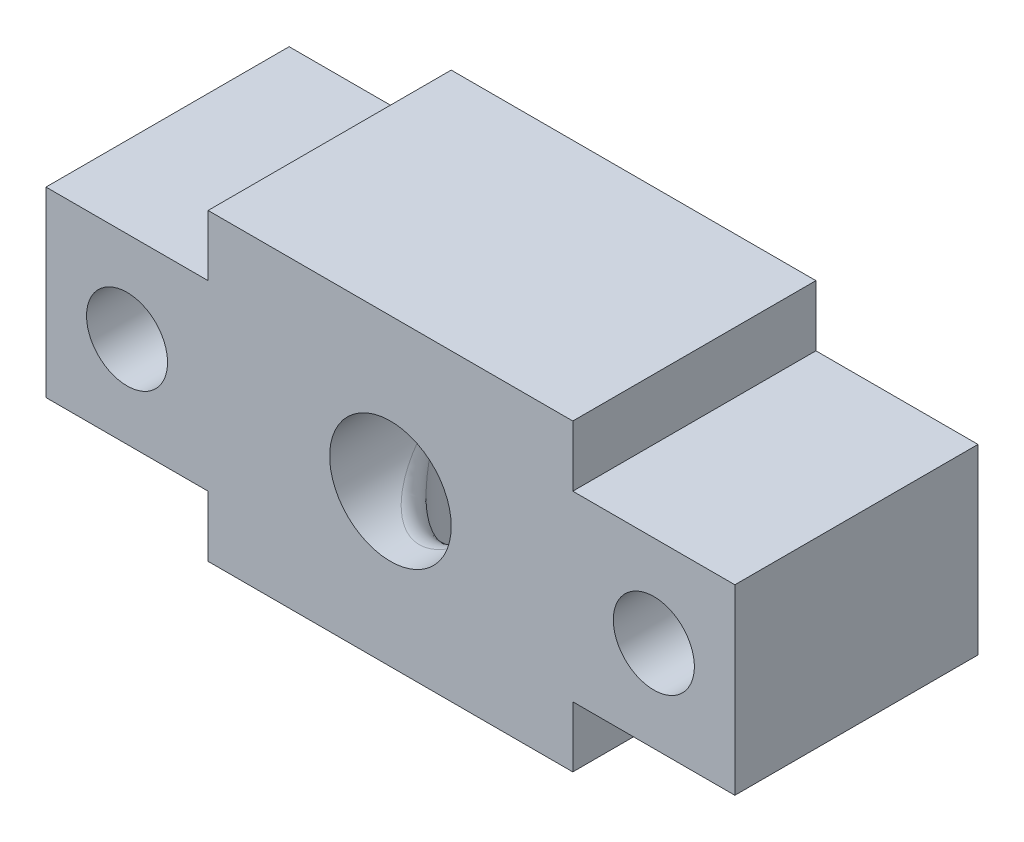
SolidWorks part; units mm, degrees
ref_plane "Front Plane" through (0, 0, 0) normal (0, 0, 1) x (1, 0, 0)
ref_plane "Top Plane" through (0, 0, 0) normal (0, 1, 0) x (1, 0, 0)
ref_plane "Right Plane" through (0, 0, 0) normal (1, 0, 0) x (0, 0, -1)
sketch "Sketch1" plane through (0, 0, 0) normal (0, 0, 1) x (1, 0, 0)
  line L1 (-107.95, 28.575) -> (107.95, 28.575)
  line L2 (-107.95, 28.575) -> (-107.95, -28.575)
  line L3 (-107.95, -28.575) -> (107.95, -28.575)
  line L4 (107.95, 28.575) -> (107.95, -28.575)
  line L5 (-107.95, 28.575) -> (107.95, -28.575) construction
  line L6 (-107.95, -28.575) -> (107.95, 28.575) construction
  line L7 (-57.15, 47.625) -> (57.15, 47.625)
  line L8 (-57.15, 47.625) -> (-57.15, -47.625)
  line L9 (-57.15, -47.625) -> (57.15, -47.625)
  line L10 (57.15, 47.625) -> (57.15, -47.625)
  line L11 (-57.15, 47.625) -> (57.15, -47.625) construction
  line L12 (-57.15, -47.625) -> (57.15, 47.625) construction
  circle A0 centre (-82.55, 0) radius 12.7
  circle A1 centre (82.55, 0) radius 12.7
  point P0 (0, 0)
  point P6 (0, 0)
  point P15 (0, 0)
  point P16 (-152.4, 0)
  point P17 (-107.95, 0)
  dimension "D5" = 25.4
  dimension "D1" = 25.4
  dimension "D2" = 19.05
  dimension "D3" = 57.15
  dimension "D4" = 114.3
  dimension "D6" = 25.4
  dimension "D7" = 25.4
extrude "Boss-Extrude1" add sketch "Sketch1" along normal blind 76.2 contours L10 L1 L8 L3 | L10 L7 L8 L1 | L8 L1 L2 L3 A0 | L10 L3 L8 L9 | L1 L10 L3 L4 A1
sketch "Sketch2" plane through (0, 0, 76.2) normal (0, 0, 1) x (1, 0, 0)
  circle A0 centre (0, 0) radius 19.05
  dimension "D1" = 38.1
sketch "Sketch3" plane through (0, -47.625, 0) normal (0, -1, 0) x (1, 0, 0)
  line L0 (57.15, 76.2) -> (57.15, 0) construction
  circle A0 centre (0, 38.1) radius 19.05
  point P2 (0, 0)
  point P6 (57.15, 38.1)
  dimension "D1" = 38.1
extrude "Cut-Extrude1" cut sketch "Sketch3" against normal blind 67.9
extrude "Cut-Extrude2" cut sketch "Sketch2" against normal up to surface (38.1 mm away)
fillet "Fillet1" radius 10 1 edges at (0, -19.05, 57.15)
